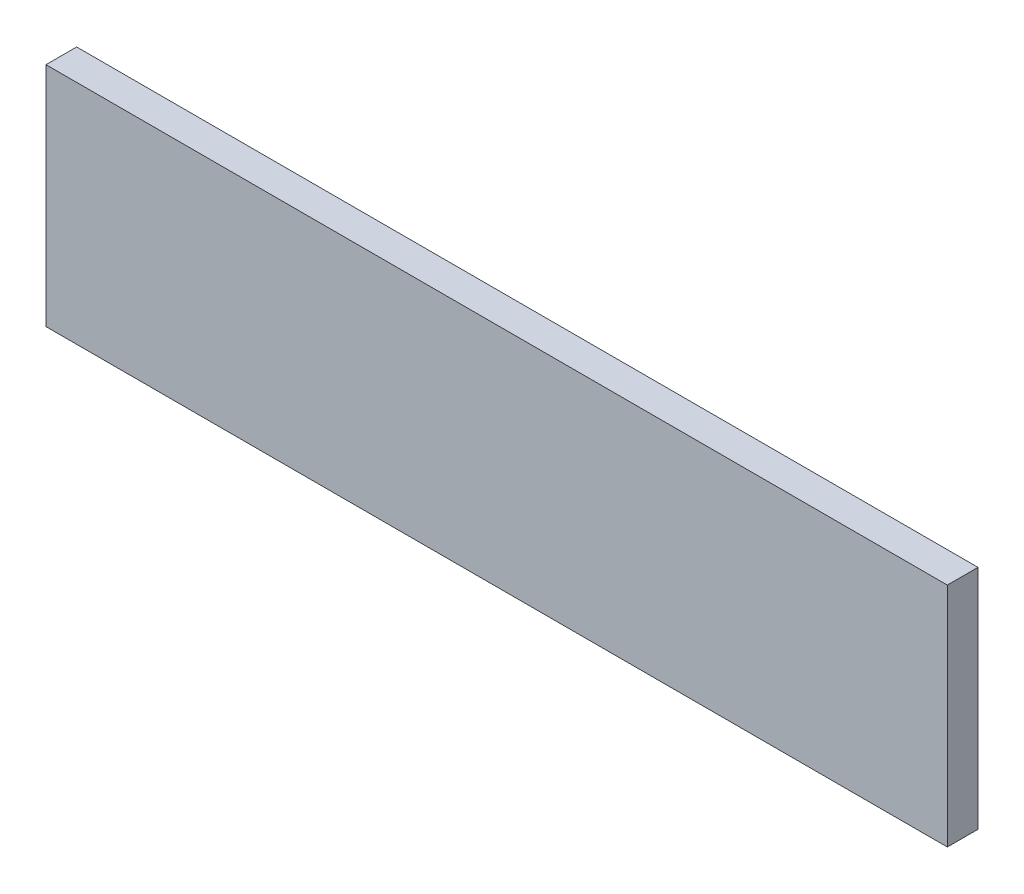
SolidWorks part; units mm, degrees
material "Plain Carbon Steel"
ref_plane "Front Plane" through (0, 0, 0) normal (0, 0, 1) x (1, 0, 0)
ref_plane "Top Plane" through (0, 0, 0) normal (0, 1, 0) x (1, 0, 0)
ref_plane "Right Plane" through (0, 0, 0) normal (1, 0, 0) x (0, 0, -1)
sketch "Sketch1" plane through (0, 0, 0) normal (0, 0, 1) x (1, 0, 0)
  line L1 (-330.3006, 99.1433) -> (-30.3006, 99.1433) construction
  line L2 (-330.3006, 99.1433) -> (-330.3006, 19.1433) construction
  line L3 (-330.3006, 19.1433) -> (-30.3006, 19.1433) construction
  line L4 (-30.3006, 99.1433) -> (-30.3006, 19.1433) construction
  line L8 (-327.3006, 96.1433) -> (-33.3006, 96.1433)
  line L9 (-33.3006, 96.1433) -> (-33.3006, 22.1433)
  line L10 (-327.3006, 22.1433) -> (-33.3006, 22.1433)
  line L11 (-327.3006, 96.1433) -> (-327.3006, 22.1433)
  line L13 (-30.3006, 99.1433) -> (-30.3006, 29.1433) construction
  line L14 (-30.3006, 99.1433) -> (-100.3006, 99.1433) construction
  line L15 (-30.3006, 19.1433) -> (-330.3006, 19.1433) construction
  line L16 (-330.3006, 99.1433) -> (-330.3006, 29.1433) construction
  dimension "D1" = 3
extrude "Boss-Extrude1" add sketch "Sketch1" along normal blind 10
